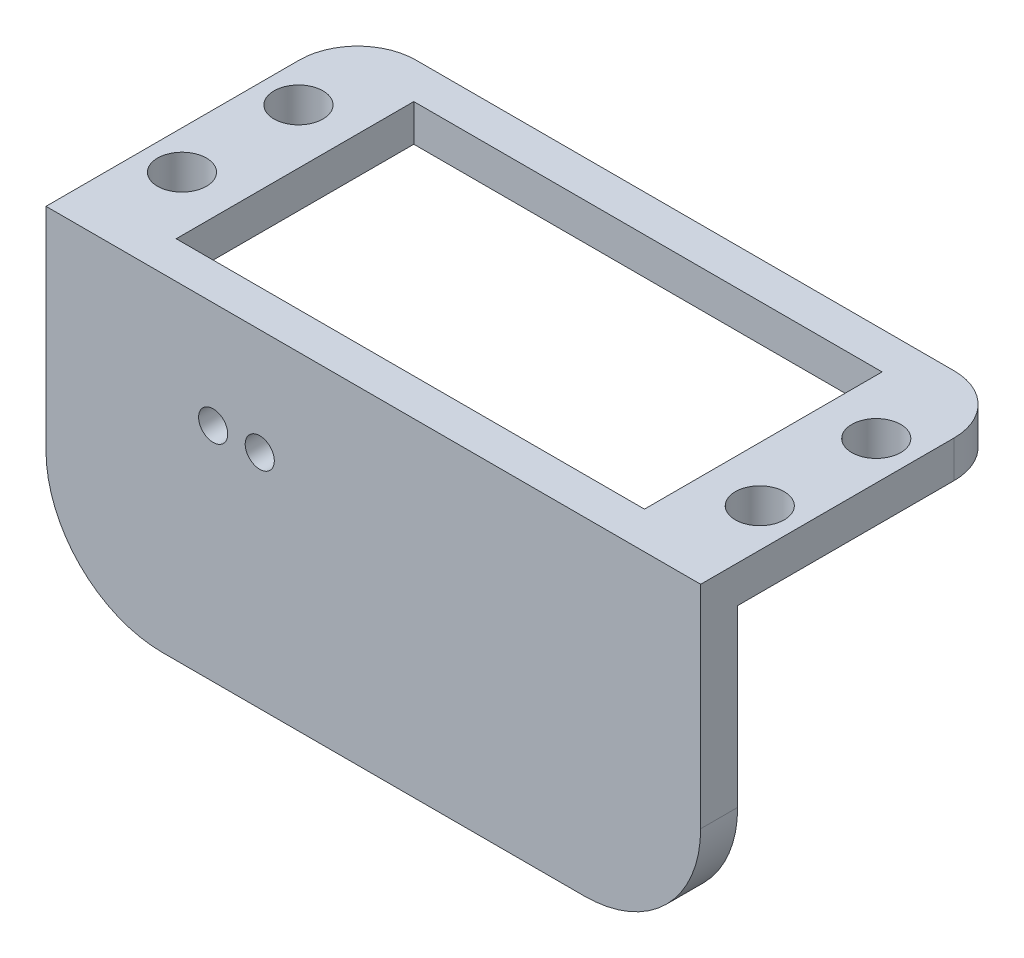
SolidWorks part; units mm, degrees
ref_plane "Front Plane" through (0, 0, 0) normal (0, 0, 1) x (1, 0, 0)
ref_plane "Top Plane" through (0, 0, 0) normal (0, 1, 0) x (1, 0, 0)
ref_plane "Right Plane" through (0, 0, 0) normal (1, 0, 0) x (0, 0, -1)
sketch "Sketch1" plane through (0, 0, 0) normal (0, 1, 0) x (1, 0, 0)
  line L0 (0, 13.375) -> (0, -13.375) construction
  line L1 (-20.1, 10.2) -> (20.1, 10.2)
  line L2 (-20.1, 10.2) -> (-20.1, -10.2)
  line L3 (-20.1, -10.2) -> (20.1, -10.2)
  line L4 (20.1, 10.2) -> (20.1, -10.2)
  line L5 (-20.1, 10.2) -> (20.1, -10.2) construction
  line L6 (-20.1, -10.2) -> (20.1, 10.2) construction
  line L7 (-28.1, 13.375) -> (28.1, 13.375)
  line L8 (-28.1, 13.375) -> (-28.1, -13.375)
  line L9 (-28.1, -13.375) -> (28.1, -13.375)
  line L10 (28.1, 13.375) -> (28.1, -13.375)
  line L11 (-28.1, 13.375) -> (28.1, -13.375) construction
  line L12 (-28.1, -13.375) -> (28.1, 13.375) construction
  circle A0 centre (24.8, 5) radius 2.1
  circle A1 centre (24.8, -5) radius 2.1
  circle A2 centre (-24.8, -5) radius 2.1
  circle A3 centre (-24.8, 5) radius 2.1
  point P0 (0, 0)
  point P6 (0, 0)
  dimension "D4" = 4.2
  dimension "D1" = 40.2
  dimension "D2" = 20.4
  dimension "D3" = 8
  dimension "D5" = 4.7
  dimension "D6" = 10
  dimension "D7" = 5.2
  dimension "D8" = 3.175
extrude "Boss-Extrude1" add sketch "Sketch1" along normal blind 3.175
sketch "Sketch2" plane through (0, 0, 0) normal (0, -1, 0) x (-1, 0, 0)
  line L0 (28.1, 13.375) -> (28.1, -13.375) construction
  line L1 (-28.1, -13.375) -> (28.1, -13.375)
  line L2 (-28.1, -13.375) -> (-28.1, -10.2)
  line L3 (-28.1, -10.2) -> (28.1, -10.2)
  line L4 (28.1, -13.375) -> (28.1, -10.2)
  line L5 (20.1, -10.2) -> (-20.1, -10.2) construction
extrude "Boss-Extrude2" add sketch "Sketch2" along normal blind 25
sketch "Sketch3" plane through (0, 0, 13.375) normal (0, 0, 1) x (1, 0, 0)
  line L0 (28.1, -5.9533) -> (-28.1, -5.9533) construction
  line L1 (28.1, 3.175) -> (28.1, -25) construction
  line L2 (-28.1, 3.175) -> (-28.1, -25) construction
  circle A0 centre (-9.75, -5.9533) radius 1.25
  circle A1 centre (-13.75, -5.9533) radius 1.25
  dimension "D1" = 2.5
  dimension "D2" = 4
  dimension "D3" = 37.85
extrude "Cut-Extrude1" cut sketch "Sketch3" against normal up to surface (3.175 mm away) up to face at (0, -5.4562, 10.2)
fillet "Fillet1" radius 10 2 edges at (-28.1, -25, 11.7875) (28.1, -25, 11.7875)
fillet "Fillet2" radius 5 2 edges at (28.1, 1.5875, -13.375) (-28.1, 1.5875, -13.375)
